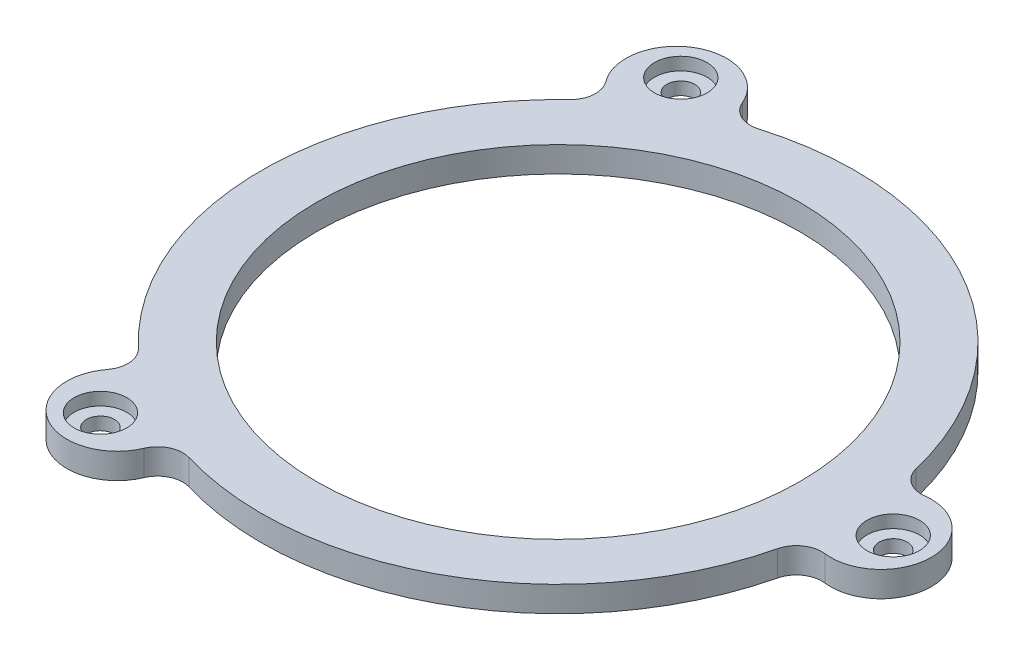
SolidWorks part; units mm, degrees
ref_plane "Front Plane" through (0, 0, 0) normal (0, 0, 1) x (1, 0, 0)
ref_plane "Top Plane" through (0, 0, 0) normal (0, 1, 0) x (1, 0, 0)
ref_plane "Right Plane" through (0, 0, 0) normal (1, 0, 0) x (0, 0, -1)
sketch "Sketch1" plane through (0, 0, 0) normal (0, 1, 0) x (1, 0, 0)
  circle A0 centre (0, 0) radius 28.5
  circle A1 centre (0, 0) radius 35
  dimension "D1" = 57
  dimension "D2" = 70
extrude "Boss-Extrude1" add sketch "Sketch1" along normal blind 3
sketch "Sketch3" plane through (0, 3, 0) normal (0, 1, 0) x (1, 0, 0)
  line L1 (0, 0) -> (44, 0) construction
  line L2 (0, 0) -> (34.6594, -4.8711) construction
  line L3 (0, 0) -> (34.6594, 4.8711) construction
  arc A1 (34.6594, 4.8711) -> (34.6594, -4.8711) centre (38.0529, 0) cw
  circle A4 centre (0, 0) radius 35 construction
  arc A5 (34.6594, 4.8711) -> (34.6594, -4.8711) centre (0, 0) cw
  arc A11 (-13.1112, -32.4514) -> (-21.5482, -27.5804) centre (-19.0265, -32.9548) cw
  arc A12 (-13.1112, -32.4514) -> (-21.5482, -27.5804) centre (0, 0) cw
  arc A13 (-21.5482, 27.5804) -> (-13.1112, 32.4514) centre (-19.0265, 32.9548) cw
  arc A14 (-21.5482, 27.5804) -> (-13.1112, 32.4514) centre (0, 0) cw
  point P17 (0, 0)
  dimension "D1" = 8
  dimension "D2" = 8
extrude "Boss-Extrude2" add sketch "Sketch3" against normal blind 3
sketch "Sketch6" plane through (0, 3, 0) normal (0, 1, 0) x (1, 0, 0)
  line L0 (0, 0) -> (39.5, 0) construction
  circle A0 centre (39.5, 0) radius 1.65
  circle A3 centre (-19.75, -34.208) radius 1.65
  circle A4 centre (-19.75, 34.208) radius 1.65
  point P11 (0, 0)
  dimension "D1" = 3.3
  dimension "D2" = 39.5
extrude "Cut-Extrude2" cut sketch "Sketch6" against normal blind 10
sketch "Sketch7" plane through (0, 3, 0) normal (0, 1, 0) x (1, 0, 0)
  circle A0 centre (39.5, 0) radius 3.1
  circle A3 centre (-19.75, -34.208) radius 3.1
  circle A4 centre (-19.75, 34.208) radius 3.1
  point P10 (1, 0.5774)
  point P11 (0, 0)
  dimension "D1" = 6.2
extrude "Cut-Extrude3" cut sketch "Sketch7" against normal blind 1.5 contours A0 | A3 | A4
fillet "Fillet1" radius 3 6 edges at (34.6594, 1.5, 4.8711) (-13.1112, 1.5, 32.4514) (-21.5482, 1.5, 27.5804) (-21.5482, 1.5, -27.5804) (-13.1112, 1.5, -32.4514) (34.6594, 1.5, -4.8711)
